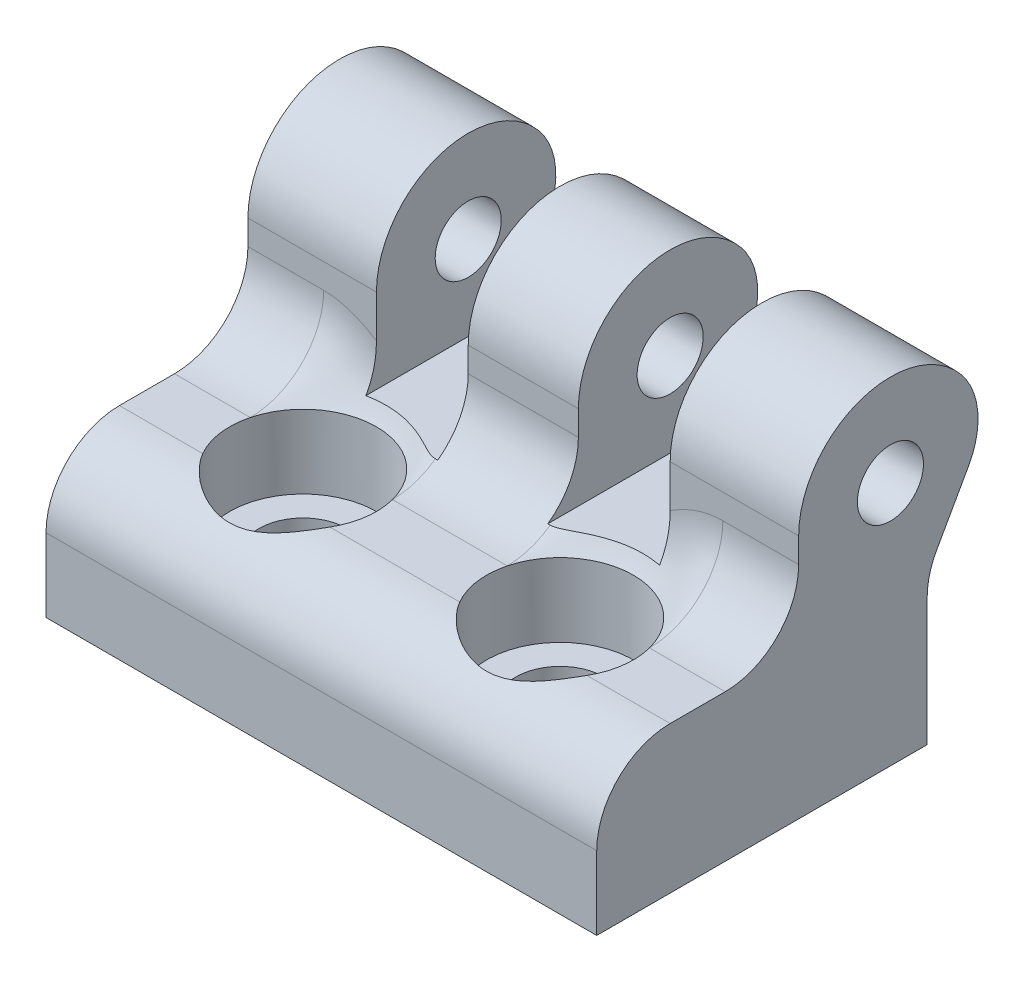
SolidWorks part; units mm, degrees
ref_plane "Front Plane" through (0, 0, 0) normal (0, 0, 1) x (1, 0, 0)
ref_plane "Top Plane" through (0, 0, 0) normal (0, 1, 0) x (1, 0, 0)
ref_plane "Right Plane" through (0, 0, 0) normal (1, 0, 0) x (0, 0, -1)
sketch "Sketch2" plane through (0, 0, 0) normal (0, 1, 0) x (1, 0, 0)
  line L1 (0, 0) -> (30, 0)
  line L2 (0, 0) -> (0, 18)
  line L3 (0, 18) -> (30, 18)
  line L4 (30, 0) -> (30, 18)
  dimension "D1" = 18
  dimension "D2" = 30
extrude "Boss-Extrude1" add sketch "Sketch2" along normal blind 8
sketch "Sketch3" plane through (0, 0, 0) normal (-1, 0, 0) x (0, 0, 1)
  line L0 (-18, 8) -> (-18, 0) construction
  line L1 (-18, 0) -> (0, 0) construction
  line L2 (-18, 8) -> (-21, 13.35)
  line L4 (-11, 13.35) -> (-11, 8)
  line L5 (-18, 8) -> (-11, 8)
  line L6 (-18, 8) -> (0, 8) construction
  arc A0 (-11, 13.35) -> (-21, 13.35) centre (-16, 13.35) ccw
  dimension "D1" = 10
  dimension "D2" = 2
  dimension "D3" = 13.35
  dimension "D4" = 0
extrude "Boss-Extrude2" add sketch "Sketch3" against normal up to surface (30 mm away) contours A0 L2 L5 L4 up to face at (30, 4, -9)
hole_wizard "CBORE for M3 SHCS1" positions "Sketch4" profile "Sketch5" counterbore size "M3" standard "ANSI Metric" end condition through all
sketch "Sketch4" plane through (0, 0, 0) normal (-1, 0, 0) x (0, 0, 1)
  arc A0 (-11, 13.35) -> (-21, 13.35) centre (-16, 13.35) ccw construction
  point P0 (-16, 13.35)
  dimension "D2" = 0
sketch "Sketch5" plane through (0, 13.35, -16) normal (0, 1, 0) x (0, 0, 1)
  line L0 (0, 0) -> (0, 30)
  line L1 (0, 30) -> (1.8, 30)
  line L3 (1.8, 30) -> (1.8, 3)
  line L4 (1.8, 3) -> (3.25, 3)
  line L5 (3.25, 3) -> (3.25, 0)
  line L7 (3.25, 0) -> (0, 0)
  line L11 (0, -6.35) -> (0, 107.95) construction
  dimension "Thru Hole Dia." = 3.6
  dimension "Thru Hole Depth" = 30
  dimension "C'Bore Dia." = 6.5
  dimension "C'Bore Depth" = 3
hole_wizard "CBORE for M4 SHCS1" positions "Sketch6" profile "Sketch7" counterbore size "M4" standard "ANSI Metric" end condition through all
sketch "Sketch6" plane through (0, 8, 0) normal (0, 1, 0) x (1, 0, 0)
  line L0 (0, 0) -> (30, 0) construction
  line L1 (0, 11) -> (0, 0) construction
  line L2 (30, 0) -> (30, 11) construction
  point P0 (8, 6)
  point P2 (22, 6)
  dimension "D1" = 6
  dimension "D2" = 8
  dimension "D3" = 6
  dimension "D4" = 8
sketch "Sketch7" plane through (8, 8, -6) normal (1, 0, 0) x (0, 0, 1)
  line L0 (0, 0) -> (0, 8)
  line L1 (0, 8) -> (2.4, 8)
  line L3 (2.4, 8) -> (2.4, 4)
  line L4 (2.4, 4) -> (4, 4)
  line L5 (4, 4) -> (4, 0)
  line L7 (4, 0) -> (0, 0)
  line L11 (0, -6.35) -> (0, 107.95) construction
  dimension "Thru Hole Dia." = 4.8
  dimension "Thru Hole Depth" = 8
  dimension "C'Bore Dia." = 8
  dimension "C'Bore Depth" = 4
fillet "Fillet1" radius 4 2 edges at (15, 8, -18) (15, 13.35, -21)
fillet "Fillet2" radius 4 2 edges at (15, 8, 0) (15, 8, -11)
sketch "Sketch8" plane through (0, 0, -18) normal (0, 0, -1) x (-1, 0, 0)
  line L0 (0, 8.9114) -> (0, 12.0303) construction
  line L1 (-30, 12.0303) -> (-30, 8.9114) construction
  line L2 (0, 8.9114) -> (0, 12.0303) construction
  line L3 (-30, 12.0303) -> (-30, 8.9114) construction
  line L5 (-18, 8.7546) -> (-23, 8.7546)
  line L6 (-18, 8.7546) -> (-18, 18.35)
  line L7 (-18, 18.35) -> (-23, 18.35)
  line L8 (-23, 8.7546) -> (-23, 18.35)
  line L9 (-30, 18.35) -> (-30, 13.35) construction
  line L10 (-7, 8.7546) -> (-12, 8.7546)
  line L11 (-7, 8.7546) -> (-7, 18.35)
  line L12 (-7, 18.35) -> (-12, 18.35)
  line L13 (-12, 8.7546) -> (-12, 18.35)
  line L14 (0, 12.0303) -> (0, 16.5336) construction
  line L15 (0, 18.35) -> (-30, 18.35) construction
  dimension "D1" = 5
  dimension "D2" = 5
  dimension "D3" = 30
  dimension "D4" = 7
  dimension "D5" = 7
  dimension "D6" = 0
  dimension "D7" = 0
extrude "Cut-Extrude1" cut sketch "Sketch8" against normal through all both and the other way through all
